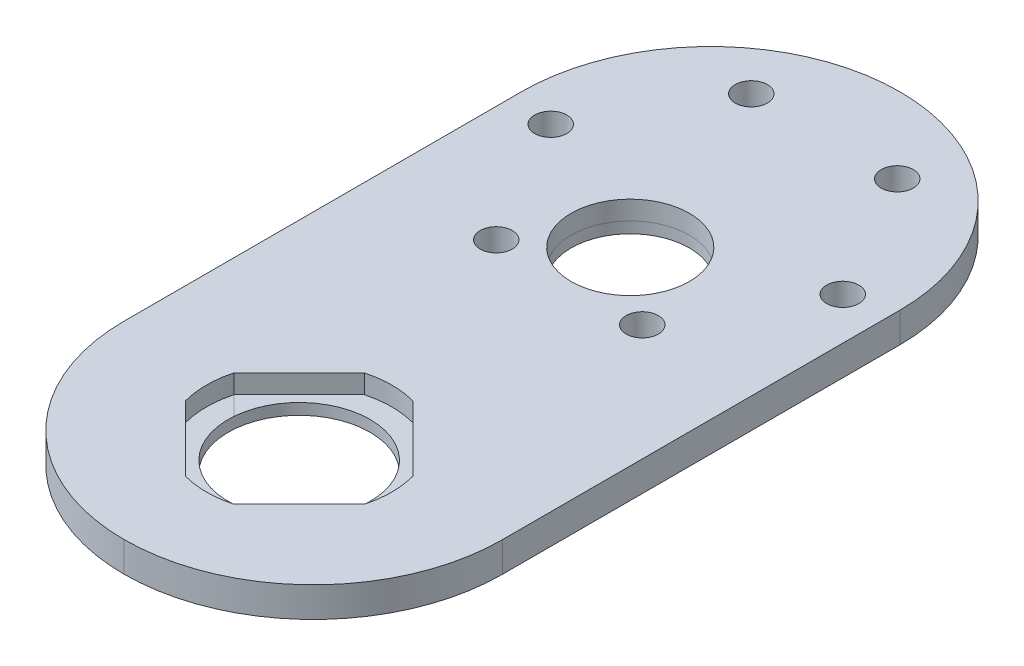
SolidWorks part; units mm, degrees
note: The reader was unsure of these and kept them because the rebuilt part matched: thickness of "Brida base1", "Chapa metálica1", "Chapa metálica5", "Chapa metálica6", "Chapa metálica7".
ref_plane "Alzado" through (0, 0, 0) normal (0, 0, 1) x (1, 0, 0)
ref_plane "Planta" through (0, 0, 0) normal (0, 1, 0) x (1, 0, 0)
ref_plane "Vista lateral" through (0, 0, 0) normal (1, 0, 0) x (0, 0, -1)
sketch "Croquis1" plane through (0, 0, 0) normal (0, 1, 0) x (1, 0, 0)
  line L1 (-60.9085, 52.2767) -> (-20.9085, 52.2767)
  line L2 (-60.9085, 52.2767) -> (-60.9085, -29.7233)
  line L3 (-60.9085, -29.7233) -> (-20.9085, -29.7233)
  line L4 (-20.9085, 52.2767) -> (-20.9085, -29.7233)
  dimension "D1" = 40
  dimension "D2" = 82
base flange "Brida base1" sketch "Croquis1" thickness 3.175 reverse thickness direction no parameters "D1"=0.7366
sketch "Croquis2" plane through (0, 0, 0) normal (0, -1, 0) x (1, 0, 0)
  line L0 (-40.9085, 11.2233) -> (-27.1029, 25.0289) construction
  line L4 (-38.347, 20.6826) -> (-31.4492, 13.7848)
  line L5 (-43.47, 20.6826) -> (-50.3678, 13.7848)
  line L6 (-50.3678, 8.6618) -> (-43.47, 1.764)
  line L7 (-31.4492, 8.6618) -> (-38.347, 1.764)
  line L8 (-27.1029, 25.0289) -> (-20.9085, 25.0289) construction
  line L9 (-39.1557, 12.9761) -> (-46.9189, 5.2129) construction
  line L10 (-20.9085, 29.7233) -> (-20.9085, -52.2767) construction
  circle A0 centre (-40.9085, -23.7767) radius 6.25
  arc A7 (-43.47, 1.764) -> (-38.347, 1.764) centre (-40.9085, 11.2233) ccw
  arc A8 (-31.4492, 8.6618) -> (-31.4492, 13.7848) centre (-40.9085, 11.2233) ccw
  arc A10 (-38.347, 20.6826) -> (-43.47, 20.6826) centre (-40.9085, 11.2233) ccw
  arc A11 (-50.3678, 13.7848) -> (-50.3678, 8.6618) centre (-40.9085, 11.2233) ccw
  point P6 (-40.9085, -6.0261)
  dimension "D3" = 9.8
  dimension "D4" = 17
  dimension "D7" = 12.5
  dimension "D1" = 17
  dimension "D2" = 8.5
  dimension "D6" = 9.755
  dimension "D8" = 35
sketch "Croquis6" plane through (0, 0, 0) normal (0, 1, 0) x (1, 0, 0)
  line L4 (-43.47, -1.764) -> (-50.3678, -8.6618)
  line L5 (-31.4492, -8.6618) -> (-38.347, -1.764)
  line L6 (-38.347, -20.6826) -> (-31.4492, -13.7848)
  line L7 (-50.3678, -13.7848) -> (-43.47, -20.6826)
  line L8 (-43.47, -1.764) -> (-50.3678, -8.6618)
  line L9 (-31.4492, -8.6618) -> (-38.347, -1.764)
  line L10 (-38.347, -20.6826) -> (-31.4492, -13.7848)
  line L11 (-50.3678, -13.7848) -> (-43.47, -20.6826)
  circle A1 centre (-40.9085, 23.7767) radius 6.25
  circle A2 centre (-40.9085, 23.7767) radius 6.25
  arc A6 (-38.347, -1.764) -> (-43.47, -1.764) centre (-40.9085, -11.2233) ccw
  arc A7 (-31.4492, -13.7848) -> (-31.4492, -8.6618) centre (-40.9085, -11.2233) ccw
  arc A8 (-43.47, -20.6826) -> (-38.347, -20.6826) centre (-40.9085, -11.2233) ccw
  arc A9 (-50.3678, -8.6618) -> (-50.3678, -13.7848) centre (-40.9085, -11.2233) ccw
  arc A10 (-38.347, -1.764) -> (-43.47, -1.764) centre (-40.9085, -11.2233) ccw
  arc A11 (-31.4492, -13.7848) -> (-31.4492, -8.6618) centre (-40.9085, -11.2233) ccw
  arc A12 (-43.47, -20.6826) -> (-38.347, -20.6826) centre (-40.9085, -11.2233) ccw
  arc A13 (-50.3678, -8.6618) -> (-50.3678, -13.7848) centre (-40.9085, -11.2233) ccw
  dimension "D1" = 0
  dimension "D2" = 0
extrude "Cortar-Extruir17" cut sketch "Croquis6" against normal blind 2 normal cut yes
sketch "Croquis5" plane through (0, -3.175, 0) normal (0, -1, 0) x (1, 0, 0)
  line L0 (-40.9085, 29.7233) -> (-40.9085, 11.2233) construction
  line L1 (-60.9085, 29.7233) -> (-20.9085, 29.7233) construction
  circle A0 centre (-40.9085, 11.2233) radius 7.5
  circle A2 centre (-40.9085, -23.7767) radius 6.25
  dimension "D1" = 15
  dimension "D2" = 18.5
extrude "Cortar-Extruir5" cut sketch "Croquis5" against normal blind 10 normal cut yes
fillet "Redondeo1" radius 20 4 edges at (-60.9085, -1.5875, -52.2767) (-20.9085, -1.5875, -52.2767) (-20.9085, -1.5875, 29.7233) (-60.9085, -1.5875, 29.7233)
hole_wizard "Taladro de margen para M31" positions "Croquis9" profile "Croquis10" hole size "M3" standard "Ansi Metric" end condition through all
sketch "Croquis9" plane through (-178.499, -3.175, 246.5193) normal (0, -1, 0) x (0.8066, 0, 0.5911)
  point P0 (-65.4616, -295.9031)
  point P3 (-67.079, -311.3184)
  point P6 (-51.3028, -289.5961)
  point P9 (-54.5376, -320.4268)
  point P12 (-40.3788, -314.1199)
  point P15 (-38.7614, -298.7045)
sketch "Croquis10" plane through (-56.378, -3.175, -30.8438) normal (1, 0, 0) x (0, 0, -1)
  line L0 (0, 0) -> (0, 3.175)
  line L1 (0, 3.175) -> (1.7, 3.175)
  line L2 (1.7, 3.175) -> (1.7, 0)
  line L3 (1.7, 0) -> (0, 0)
  line L4 (0, -6.35) -> (0, 107.95) construction
  dimension "Diámetro de taladro hasta el siguiente" = 3.4
  dimension "Profundidad de taladro hasta el siguiente" = 3.175
sketch "Líneas de pliegue1" [suppressed] plane through (0, 0, 0) normal (0, 1, 0) x (1, 0, 0)
sketch "Cuadro delimitador1" [suppressed] plane through (0, 0, 0) normal (0, 1, 0) x (1, 0, 0)
sheet metal parameters "Chapa metálica1" thickness 3.175 parameters "D1"=0.7366
flat pattern "Chapa desplegada1" [suppressed]
sketch "Líneas de pliegue2" plane through (0, 0, 0) normal (0, 1, 0) x (1, 0, 0)
sketch3d "Cuadro delimitador2" [suppressed]
  line L0 (-60.9085, 52.2767, 0) -> (-60.9085, -29.7233, 0) construction
  line L1 (-20.9085, 52.2767, 0) -> (-20.9085, -29.7233, 0) construction
  line L2 (-60.9085, 52.2767, 0) -> (-20.9085, 52.2767, 0) construction
  line L3 (-60.9085, -29.7233, 0) -> (-20.9085, -29.7233, 0) construction
sheet metal parameters "Chapa metálica5" thickness 3.175 parameters "D1"=0.7366, "D7"=1.5875
flat pattern "Chapa desplegada1"
sketch "Líneas de pliegue2" plane through (0, 0, 0) normal (0, 1, 0) x (1, 0, 0)
sketch3d "Cuadro delimitador2" [suppressed]
  line L0 (-60.9085, 52.2767, 0) -> (-60.9085, -29.7233, 0) construction
  line L1 (-20.9085, 52.2767, 0) -> (-20.9085, -29.7233, 0) construction
  line L2 (-60.9085, 52.2767, 0) -> (-20.9085, 52.2767, 0) construction
  line L3 (-60.9085, -29.7233, 0) -> (-20.9085, -29.7233, 0) construction
sheet metal parameters "Chapa metálica6" thickness 3.175 parameters "D1"=0.7366, "D7"=1.5875
flat pattern "Chapa desplegada1"
sketch "Líneas de pliegue2" plane through (0, 0, 0) normal (0, 1, 0) x (1, 0, 0)
sketch3d "Cuadro delimitador2" [suppressed]
  line L0 (-60.9085, 52.2767, 0) -> (-60.9085, -29.7233, 0) construction
  line L1 (-20.9085, 52.2767, 0) -> (-20.9085, -29.7233, 0) construction
  line L2 (-60.9085, 52.2767, 0) -> (-20.9085, 52.2767, 0) construction
  line L3 (-60.9085, -29.7233, 0) -> (-20.9085, -29.7233, 0) construction
sheet metal parameters "Chapa metálica7" thickness 3.175 parameters "D1"=0.7366, "D7"=1.5875
flat pattern "Chapa desplegada1"
sketch "Líneas de pliegue2" plane through (0, 0, 0) normal (0, 1, 0) x (1, 0, 0)
sketch3d "Cuadro delimitador2" [suppressed]
  line L0 (-60.9085, 52.2767, 0) -> (-60.9085, -29.7233, 0) construction
  line L1 (-20.9085, 52.2767, 0) -> (-20.9085, -29.7233, 0) construction
  line L2 (-60.9085, 52.2767, 0) -> (-20.9085, 52.2767, 0) construction
  line L3 (-60.9085, -29.7233, 0) -> (-20.9085, -29.7233, 0) construction
